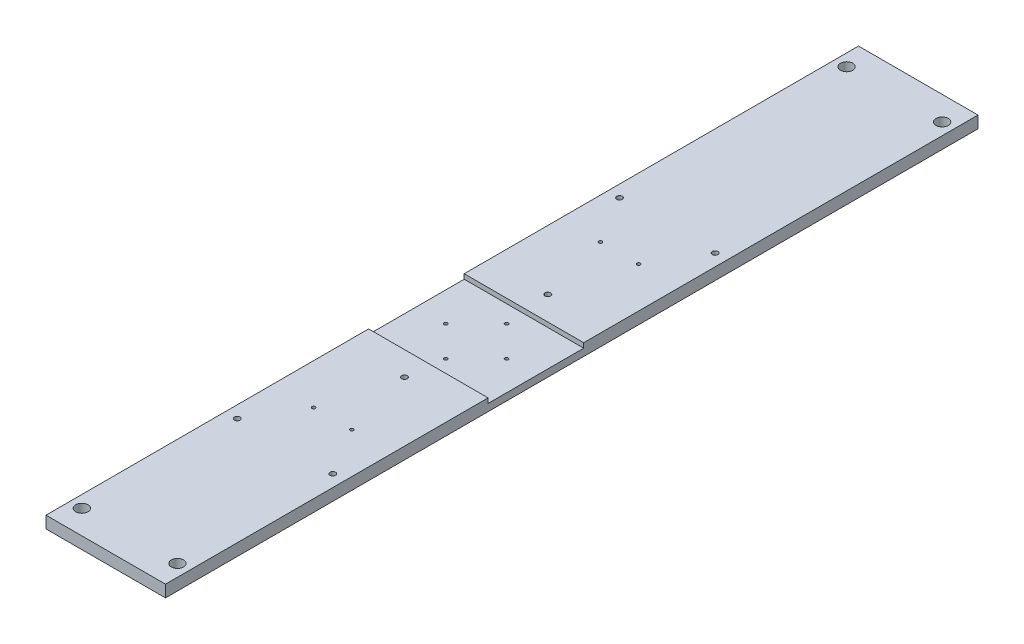
SolidWorks part; units mm, degrees
ref_plane "Front" through (0, 0, 0) normal (0, 0, 1) x (1, 0, 0)
ref_plane "Top" through (0, 0, 0) normal (0, 1, 0) x (1, 0, 0)
ref_plane "Right" through (0, 0, 0) normal (1, 0, 0) x (0, 0, -1)
sketch "Sketch1" plane through (0, 0, 0) normal (0, 1, 0) x (1, 0, 0)
  line L1 (0, 0) -> (63.5, 0)
  line L2 (0, 0) -> (0, 431.8)
  line L3 (0, 431.8) -> (63.5, 431.8)
  line L4 (63.5, 0) -> (63.5, 431.8)
  dimension "D1" = 431.8
  dimension "D2" = 63.5
extrude "Boss-Extrude1" add sketch "Sketch1" along normal blind 6.35
sketch "Sketch3" plane through (0, 6.35, 0) normal (0, 1, 0) x (1, 0, 0)
  line L0 (0, 0) -> (63.5, 0) construction
  line L1 (0, 431.8) -> (0, 0) construction
  line L2 (31.75, 431.8) -> (31.75, 0) construction
  line L3 (63.5, 431.8) -> (0, 431.8) construction
  line L6 (0, 165.1) -> (0, 228.6)
  line L9 (0, 196.85) -> (139.7, 196.85) construction
  circle A0 centre (3.175, 3.175) radius 1.1303
  circle A1 centre (3.175, 161.925) radius 1.1303
  circle A2 centre (3.175, 390.525) radius 1.1303
  circle A3 centre (3.175, 231.775) radius 1.1303
  circle A4 centre (60.325, 3.175) radius 1.1303
  circle A5 centre (60.325, 161.925) radius 1.1303
  circle A6 centre (60.325, 231.775) radius 1.1303
  circle A7 centre (60.325, 390.525) radius 1.1303
  dimension "D1" = 2.2606
  dimension "D2" = 3.175
  dimension "D3" = 3.175
  dimension "D5" = 63.5
  dimension "D4" = 2
sketch "Sketch6" plane through (0, 6.35, 0) normal (0, 1, 0) x (1, 0, 0)
  line L0 (63.5, 431.8) -> (0, 431.8) construction
  line L1 (0, 431.8) -> (0, 0) construction
  line L2 (31.75, 431.8) -> (31.75, 0) construction
  line L3 (0, 0) -> (63.5, 0) construction
  line L4 (31.75, 215.9) -> (94.2364, 215.9) construction
  circle A0 centre (6.35, 419.1) radius 3.2639
  circle A1 centre (57.15, 419.1) radius 3.2639
  circle A4 centre (57.15, 12.7) radius 3.2639
  circle A5 centre (6.35, 12.7) radius 3.2639
  point P13 (31.75, 215.9)
  dimension "D1" = 6.5278
  dimension "D2" = 12.7
  dimension "D3" = 6.35
extrude "Cut-Extrude9" cut sketch "Sketch6" against normal through all
sketch "Sketch7" plane through (0, 6.35, 0) normal (0, 1, 0) x (1, 0, 0)
  line L0 (0, 393.7) -> (63.5, 393.7) construction
  line L1 (0, 431.8) -> (0, 0) construction
  line L2 (63.5, 0) -> (63.5, 431.8) construction
  line L3 (0, 196.85) -> (139.7, 196.85) construction
  line L4 (31.75, 0) -> (31.75, 431.8) construction
  line L5 (0, 196.85) -> (63.5, 196.85) construction
  circle A0 centre (6.35, 298.45) radius 1.4732
  circle A1 centre (3.175, 390.525) radius 1.1303 construction
  circle A2 centre (57.15, 298.45) radius 1.4732
  circle A3 centre (57.15, 95.25) radius 1.4732
  circle A4 centre (6.35, 95.25) radius 1.4732
  circle A5 centre (31.75, 234.95) radius 1.4732
  circle A8 centre (31.75, 158.75) radius 1.4732
  dimension "D1" = 3.175
  dimension "D2" = 101.6
  dimension "D3" = 2.9464
  dimension "D4" = 6.35
  dimension "D5" = 2.9464
  dimension "D6" = 63.5
extrude "Cut-Extrude10" cut sketch "Sketch7" against normal through all
sketch "Sketch8" plane through (0, 6.35, 0) normal (0, 1, 0) x (1, 0, 0)
  line L0 (31.75, 0) -> (31.75, 431.8) construction
  line L1 (0, 196.85) -> (63.5, 196.85) construction
  line L2 (63.5, 0) -> (63.5, 431.8) construction
  circle A0 centre (15.5854, 196.85) radius 0.889
  circle A1 centre (31.75, 213.0146) radius 0.889
  circle A2 centre (47.9146, 196.85) radius 0.889
  circle A3 centre (31.75, 180.6854) radius 0.889
  circle A4 centre (21.59, 273.05) radius 0.889
  circle A5 centre (6.35, 298.45) radius 1.4732 construction
  circle A6 centre (41.91, 273.05) radius 0.889
  circle A7 centre (41.91, 120.65) radius 0.889
  circle A8 centre (21.59, 120.65) radius 0.889
  point P11 (31.75, 196.85)
  point P20 (31.75, 196.85)
  dimension "D1" = 1.778
  dimension "D2" = 16.1646
  dimension "D4" = 1.778
  dimension "D5" = 25.4
  dimension "D6" = 10.16
  dimension "D3" = 4
extrude "Cut-Extrude11" cut sketch "Sketch8" against normal through all
sketch "Sketch9" plane through (0, 6.35, 0) normal (0, 1, 0) x (1, 0, 0)
  line L0 (31.75, 431.8) -> (31.75, 0) construction
  line L1 (31.75, 0) -> (139.7, 196.85) construction
  line L2 (139.7, 196.85) -> (0, 196.85) construction
  line L3 (63.5, 0) -> (63.5, 431.8) construction
  line L4 (0, 171.45) -> (63.5, 171.45)
  line L5 (0, 171.45) -> (0, 222.25)
  line L6 (0, 222.25) -> (63.5, 222.25)
  line L7 (63.5, 171.45) -> (63.5, 222.25)
  line L8 (0, 171.45) -> (63.5, 222.25) construction
  line L9 (0, 222.25) -> (63.5, 171.45) construction
  point P2 (31.75, 196.85)
  dimension "D1" = 50.8
extrude "Cut-Extrude12" cut sketch "Sketch9" against normal blind 2.54
